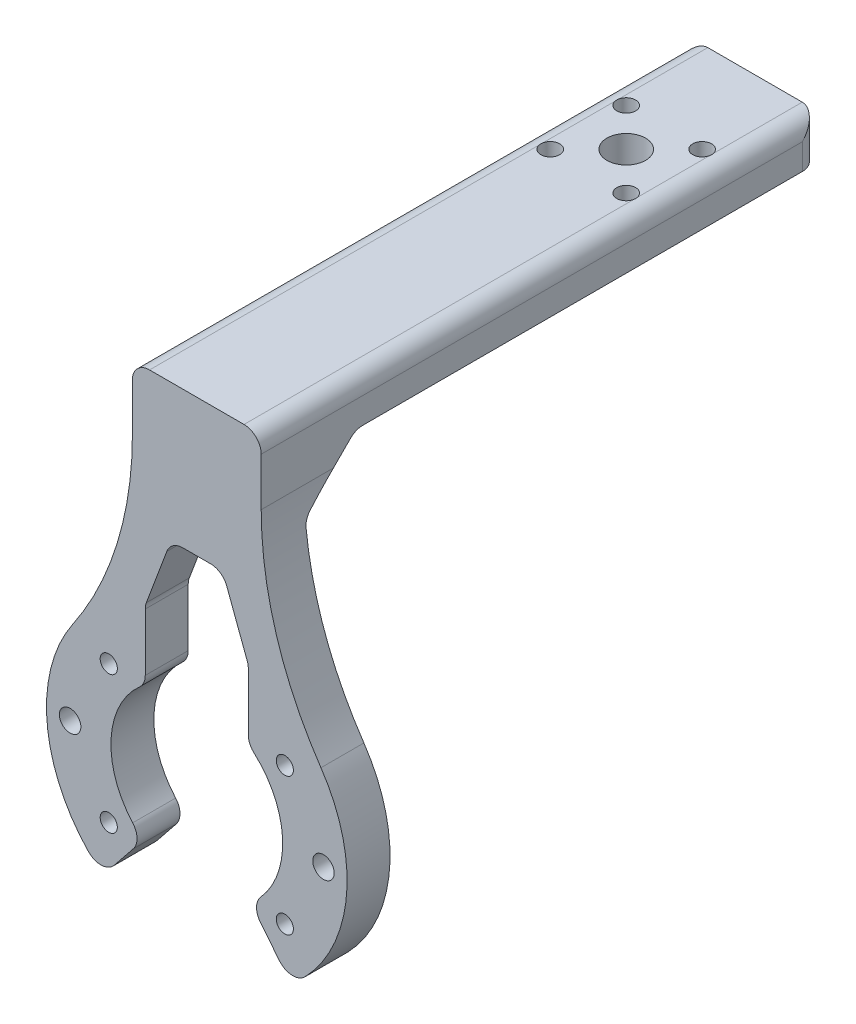
SolidWorks part; units mm, degrees
material "ABS"
ref_plane "前视基准面" through (0, 0, 0) normal (0, 0, 1) x (1, 0, 0)
ref_plane "上视基准面" through (0, 0, 0) normal (0, 1, 0) x (1, 0, 0)
ref_plane "右视基准面" through (0, 0, 0) normal (1, 0, 0) x (0, 0, -1)
sketch "草图1" plane through (0, 0, 0) normal (0, 0, 1) x (1, 0, 0)
  line L0 (19.25, 0) -> (-19.25, 0) construction
  line L1 (0, -23.511) -> (0, 23.511) construction
  line L2 (-7.5, 15.8114) -> (-7.5, 40)
  line L3 (7.5, 15.8114) -> (7.5, 40)
  line L4 (0, 0) -> (-10.939, -13.6597)
  line L5 (0, 0) -> (10.939, -13.6597)
  line L6 (-7.5, 40) -> (7.5, 40)
  circle A0 centre (-10.25, 8) radius 1
  circle A1 centre (-14.75, 0) radius 1.25
  circle A2 centre (-10.25, -8) radius 1
  circle A3 centre (10.25, -8) radius 1
  circle A4 centre (14.75, 0) radius 1.25
  circle A5 centre (10.25, 8) radius 1
  circle A6 centre (0, 0) radius 10
  circle A7 centre (0, 0) radius 17.5
  dimension "D1" = 29.5
  dimension "D2" = 20.5
  dimension "D3" = 16
  dimension "D4" = 2
  dimension "D5" = 2.5
  dimension "D7" = 20
  dimension "D8" = 3.0024
  dimension "D9" = 35
  dimension "D6" = 3
  dimension "D10" = 15
  dimension "D11" = 40
extrude "凸台-拉伸1" add sketch "草图1" along normal blind 5 contours A7 L4 A6 L5 A5 A2 A1 A0 A3 A4 | A7 L3 L6 L2 region at (0, 28.4688, 0) region at (0, 17.0314, 0)
sketch "草图3" plane through (0, 0, 0) normal (1, 0, 0) x (0, 0, -1)
  line L0 (0, 40) -> (60, 40)
  line L1 (60, 40) -> (60, 35)
  line L2 (60, 35) -> (6, 35)
  line L3 (6, 35) -> (0, 29)
  line L4 (0, 15.8114) -> (0, 40) construction
  line L5 (0, 40) -> (0, 29)
  dimension "D1" = 5
  dimension "D2" = 45
  dimension "D3" = 6
  dimension "D4" = 60
extrude "凸台-拉伸2" add sketch "草图3" along normal mid plane 15
sketch "草图5" plane through (0, 35, 0) normal (0, -1, 0) x (1, 0, 0)
  circle A0 centre (0, -45) radius 6.25 construction
  circle A1 centre (-4.4194, -40.5806) radius 1
  circle A2 centre (4.4194, -40.5806) radius 1
  circle A3 centre (4.4194, -49.4194) radius 1
  circle A4 centre (-4.4194, -49.4194) radius 1
  circle A5 centre (0, -45) radius 2.25
  point P14 (0, -45)
  dimension "D2" = 12.5
  dimension "D3" = 2
  dimension "D4" = 4
  dimension "D5" = 4.5
  dimension "D1" = 45
extrude "切除-拉伸1" cut sketch "草图5" against normal blind 15 contours A5
fillet "圆角2" radius 40 2 edges at (-7.5, 15.8114, 2.5) (7.5, 15.8114, 2.5)
sketch "草图8" plane through (0, 35, 0) normal (0, -1, 0) x (-1, 0, 0)
  point P0 (4.4194, 40.5806)
  point P3 (-4.4194, 40.5806)
  point P6 (-4.4194, 49.4194)
  point P9 (4.4194, 49.4194)
hole_wizard "M2 六角圆柱头螺钉的柱形沉头孔1" positions "草图8" profile "草图7" counterbore size "M2" standard "GB" end condition through all
sketch "草图7" plane through (-4.4194, 35, -40.5806) normal (1, 0, 0) x (0, 0, -1)
  line L0 (0, 0) -> (0, 5)
  line L1 (0, 5) -> (1.1, 5)
  line L3 (1.1, 5) -> (1.1, 2.3)
  line L4 (1.1, 2.3) -> (2.15, 2.3)
  line L5 (2.15, 2.3) -> (2.15, 0)
  line L7 (2.15, 0) -> (0, 0)
  line L11 (0, -6.35) -> (0, 107.95) construction
  dimension "通孔孔直径" = 2.2
  dimension "通孔孔深度" = 5
  dimension "柱形沉头孔直径" = 4.3
  dimension "柱形沉头孔深度" = 2.3
sketch "草图9" plane through (0, 0, 5) normal (0, 0, 1) x (1, 0, 0)
  line L1 (-3, 24) -> (-6, 16)
  line L2 (-6, 8) -> (6, 8)
  line L3 (-6, 8) -> (-6, 16)
  line L5 (6, 8) -> (6, 16)
  line L8 (-3, 24) -> (3, 24)
  line L10 (3, 24) -> (6, 16)
  arc A1 (6.2509, -7.8056) -> (-6.2509, -7.8056) centre (0, 0) ccw construction
  point P12 (0, 24)
  dimension "D2" = 12
  dimension "D3" = 6
  dimension "D4" = 8
  dimension "D5" = 8
extrude "切除-拉伸2" cut sketch "草图9" against normal through all
fillet "圆角1" radius 2 16 edges at (10.939, -13.6597, 2.5) (6.2509, -7.8056, 2.5) (-6.2509, -7.8056, 2.5) (-10.939, -13.6597, 2.5) (-7.5, 40, -27.5) (7.5, 40, -27.5) (0, 29, 0) (0, 35, -6) (-7.5, 37.5, -60) (7.5, 37.5, -60) (-6, 8, 2.5) (6, 8, 2.5) (6, 16, 2.5) (3, 24, 2.5) (-6, 16, 2.5) (-3, 24, 2.5)
